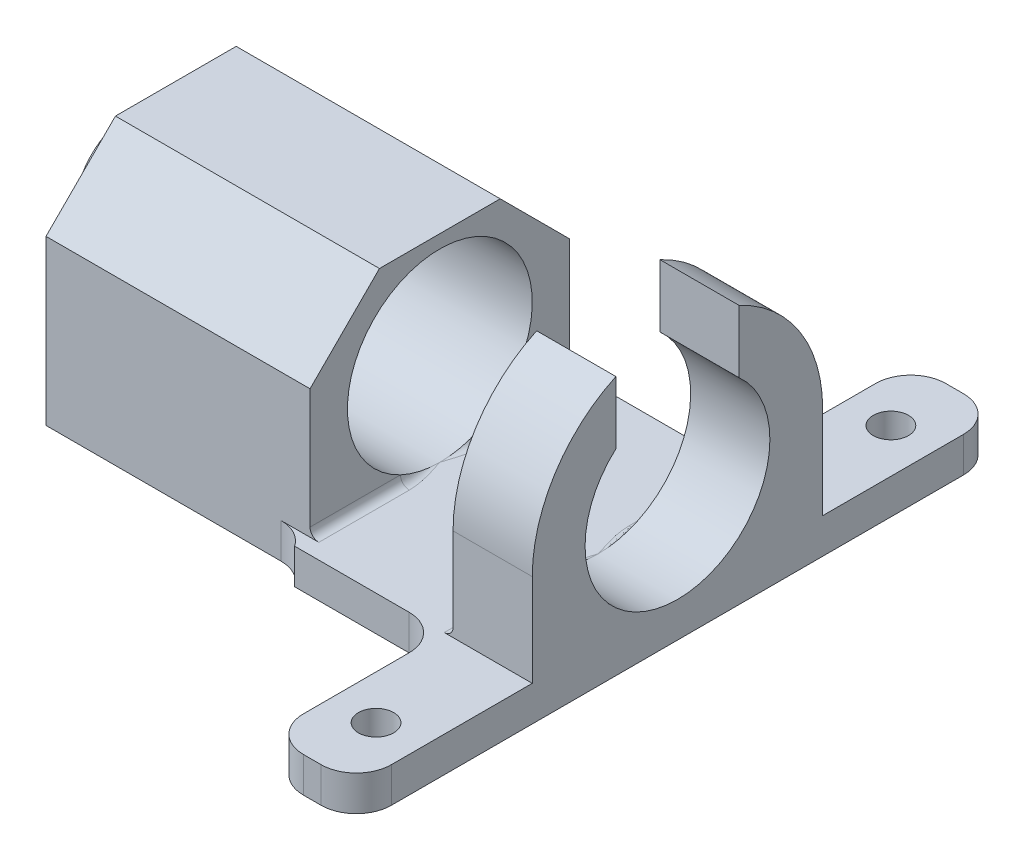
SolidWorks part; units mm, degrees
ref_plane "Front Plane" through (0, 0, 0) normal (0, 0, 1) x (1, 0, 0)
ref_plane "Top Plane" through (0, 0, 0) normal (0, 1, 0) x (1, 0, 0)
ref_plane "Right Plane" through (0, 0, 0) normal (1, 0, 0) x (0, 0, -1)
sketch "Sketch2" plane through (0, 0, 0) normal (1, 0, 0) x (0, 0, -1)
  line L0 (0, 3) -> (0, 24) construction
  line L1 (0, 3) -> (0, -1) construction
  line L2 (16.5, -1) -> (-16.5, -1)
  line L3 (-16.5, -1) -> (-16.5, 13.5)
  line L4 (16.5, -1) -> (16.5, 13.5)
  circle A0 centre (0, 13.5) radius 10.5
  arc A1 (-16.5, 13.5) -> (16.5, 13.5) centre (0, 13.5) cw
  point P11 (0, -1)
  dimension "D2" = 21
  dimension "D1" = 4
extrude "Boss-Extrude2" add sketch "Sketch2" along normal blind 30
sketch "Sketch3" plane through (30, 0, 0) normal (1, 0, 0) x (0, 0, -1)
  line L0 (-16.5, -1) -> (16.5, -1)
  line L1 (16.5, -1) -> (16.5, 3)
  line L2 (16.5, -1) -> (16.5, 13.5) construction
  line L3 (16.5, 3) -> (-16.5, 3)
  line L4 (-16.5, 13.5) -> (-16.5, -1) construction
  line L5 (-16.5, 3) -> (-16.5, -1)
  dimension "D1" = 4
extrude "Boss-Extrude3" add sketch "Sketch3" along normal blind 18
sketch "Sketch5" plane through (0, 0, 0) normal (-1, 0, 0) x (0, 0, 1)
  line L0 (-10.5, 13.5) -> (10.5, 13.5) construction
  line L1 (-7.8262, 20.5) -> (7.8262, 20.5)
  line L2 (-7.8262, 6.5) -> (7.8262, 6.5)
  circle A0 centre (0, 13.5) radius 10.5 construction
  circle A1 centre (0, 13.5) radius 6
  arc A7 (7.8262, 20.5) -> (7.8262, 6.5) centre (0, 13.5) cw
  arc A8 (-7.8262, 20.5) -> (-7.8262, 6.5) centre (0, 13.5) ccw
  circle M10 centre (0, 13.5) radius 10.5
  dimension "D2" = 12
  dimension "D1" = 7
  dimension "D3" = 7
extrude "Boss-Extrude5" add sketch "Sketch5" against normal blind 0.85 contours L0 A1 L1 M10 | L0 L2 A1 M10 region at (0, 19.7214, 0) region at (0, 13.2786, 8.25)
sketch "Sketch6" plane through (48, 0, 0) normal (1, 0, 0) x (0, 0, -1)
  line L1 (-7, 21.3262) -> (-7, 28.4416)
  line L2 (7, 21.3262) -> (7, 28.4416)
  line L3 (-16.5, -1) -> (16.5, -1)
  line L4 (-16.5, 13.5) -> (-16.5, -1)
  line L5 (16.5, -1) -> (16.5, 13.5)
  line L6 (-16.5, -1) -> (16.5, -1)
  line L7 (-16.5, 13.5) -> (-16.5, -1)
  line L8 (16.5, -1) -> (16.5, 13.5)
  arc A0 (-7, 28.4416) -> (-16.5, 13.5) centre (0, 13.5) ccw
  circle A1 centre (0, 13.5) radius 10.5
  arc A2 (-7, 21.3262) -> (7, 21.3262) centre (0, 13.5) ccw
  arc A3 (16.5, 13.5) -> (-16.5, 13.5) centre (0, 13.5) ccw
  arc A4 (16.5, 13.5) -> (7, 28.4416) centre (0, 13.5) ccw
  dimension "D3" = 14
  dimension "D1" = 0
  dimension "D2" = 0
extrude "Boss-Extrude6" add sketch "Sketch6" along normal blind 9
sketch "Sketch7" plane through (0, 0, -16.5) normal (0, 0, -1) x (-1, 0, 0)
  line L1 (-48, 3) -> (-30, 3) construction
  line L2 (-57, -1) -> (0, -1) construction
  line L7 (-57, 3) -> (-57, -1)
  line L8 (-57, -1) -> (-47, -1)
  line L9 (-47, -1) -> (-47, 3)
  line L10 (-47, 3) -> (-57, 3)
  dimension "D3" = 10
extrude "Boss-Extrude7" add sketch "Sketch7" along normal blind 20
sketch "Sketch8" plane through (0, 0, 16.5) normal (0, 0, 1) x (1, 0, 0)
  line L1 (48, 3) -> (30, 3) construction
  line L2 (57, -1) -> (0, -1) construction
  line L7 (57, -1) -> (57, 3)
  line L8 (57, 3) -> (47, 3)
  line L9 (47, 3) -> (47, -1)
  line L10 (47, -1) -> (57, -1)
  dimension "D3" = 10
extrude "Boss-Extrude8" add sketch "Sketch8" along normal blind 20
fillet "Fillet16" radius 4 2 edges at (47, 1, -16.5) (47, 1, 16.5)
fillet "Fillet15" radius 4 4 edges at (47, 1, -36.5) (57, 1, -36.5) (47, 1, 36.5) (57, 1, 36.5)
fillet "Fillet4" radius 1 4 edges at (0.425, 6.5, -7.8262) (0.425, 6.5, 7.8262) (0.425, 20.5, 7.8262) (0.425, 20.5, -7.8262)
sketch "Sketch9" plane through (0, 0, 0) normal (-1, 0, 0) x (0, 0, 1)
  line L0 (0, -1) -> (0, 30) construction
  line L1 (16.5, -1) -> (-16.5, -1) construction
  line L3 (-14.75, -1) -> (-14.75, 17.61)
  line L4 (-14.75, 17.61) -> (-6.86, 25.5)
  line L5 (-6.86, 25.5) -> (6.86, 25.5)
  line L6 (14.75, -1) -> (14.75, 17.61)
  line L7 (14.75, 17.61) -> (6.86, 25.5)
  line L9 (16.5, 13.5) -> (16.5, -1)
  line L11 (14.75, -1) -> (16.5, -1)
  line L12 (-16.5, 13.5) -> (-16.5, -1)
  line L13 (-16.5, -1) -> (-14.75, -1)
  arc A0 (16.5, 13.5) -> (-16.5, 13.5) centre (0, 13.5) ccw construction
  arc A1 (-16.5, 13.5) -> (16.5, 13.5) centre (0, 13.5) cw
  point P12 (0, 25.5)
  dimension "D1" = 14.75
  dimension "D2" = 18.61
  dimension "D3" = 135
  dimension "D4" = 6.86
extrude "Cut-Extrude1" cut sketch "Sketch9" against normal up to surface (30 mm away) up to face at (30, 11, -1.75)
fillet "Fillet7" radius 1 4 edges at (30, 3, -7.375) (30, 3, 7.375) (48, 3, -8.25) (48, 3, 8.25)
sketch "Sketch11" plane through (0, 0, 0) normal (-1, 0, 0) x (0, 0, 1)
  line L0 (14.75, 13.5) -> (-14.75, 13.5) construction
  line L1 (-14.75, -1) -> (-14.75, 17.61) construction
  circle A0 centre (-7.5, 13.5) radius 1
  circle A1 centre (7.5, 13.5) radius 1
  point P6 (0, 13.5)
  dimension "D3" = 2
  dimension "D4" = 2
  dimension "D1" = 7.5
  dimension "D2" = 7.5
extrude "Cut-Extrude3" cut sketch "Sketch11" against normal up to surface (0.85 mm away) up to face at (0.85, 13.5, 6)
fillet "Fillet17" radius 4 2 edges at (30, 1, 14.75) (30, 1, -14.75)
sketch "Sketch12" plane through (0, 3, 0) normal (0, 1, 0) x (1, 0, 0)
  line L0 (52, 36.5) -> (52, -36.5) construction
  line L1 (51, 36.5) -> (53, 36.5) construction
  line L2 (53, -36.5) -> (51, -36.5) construction
  circle A0 centre (52, 29.25) radius 2
  circle A1 centre (52, -29.25) radius 2
  point P10 (52, 0)
  dimension "D3" = 4
  dimension "D4" = 4
  dimension "D1" = 29.25
  dimension "D2" = 29.25
extrude "Cut-Extrude4" cut sketch "Sketch12" against normal up to next
sketch "Sketch13" plane through (0, 0, 0) normal (-1, 0, 0) x (0, 0, 1)
  circle A0 centre (0, 13.5) radius 6
  circle A1 centre (0, 13.5) radius 6.4777
extrude "Boss-Extrude9" add sketch "Sketch13" along normal blind 5
